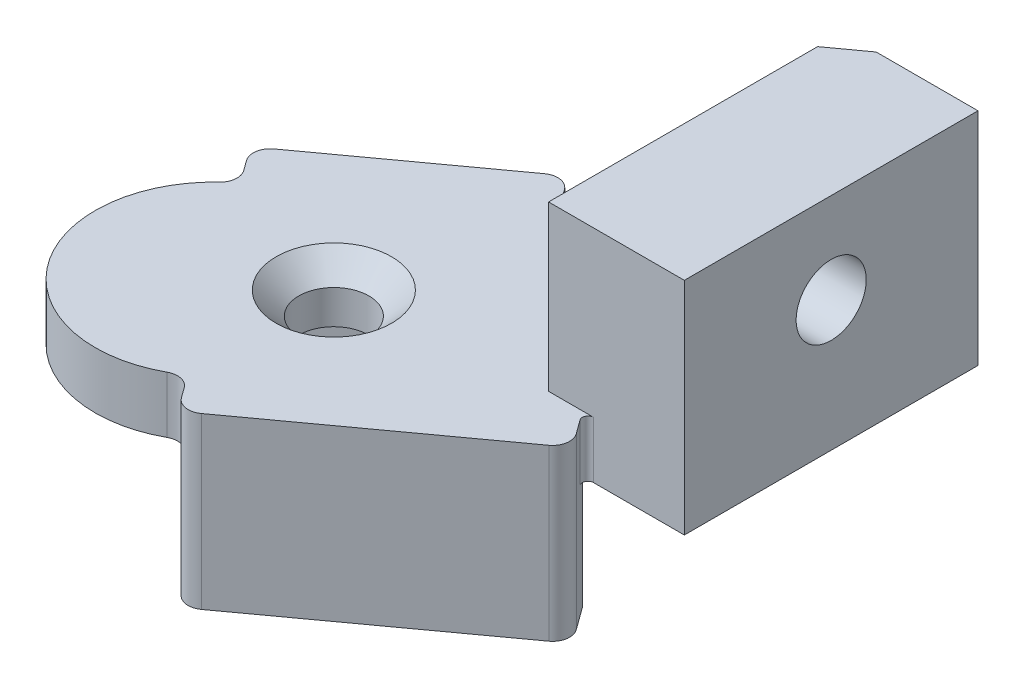
SolidWorks part; units mm, degrees
material "PA 类型 6"
ref_plane "前视基准面" through (0, 0, 0) normal (0, 0, 1) x (1, 0, 0)
ref_plane "上视基准面" through (0, 0, 0) normal (0, 1, 0) x (1, 0, 0)
ref_plane "右视基准面" through (0, 0, 0) normal (1, 0, 0) x (0, 0, -1)
sketch "草图1" plane through (0, 0, 0) normal (0, 1, 0) x (1, 0, 0)
  line L0 (0, 0) -> (0, 12.2017) construction
  line L1 (0, 0) -> (15.21, 0) construction
  line L2 (0, 0) -> (11.3188, 8.2236) construction
  line L3 (10.1244, 13.8452) -> (-6.1542, 2.018)
  line L4 (10.1244, 0.8664) -> (0.0175, -6.4766)
  line L5 (0.0175, -6.4766) -> (-6.1542, 2.018) construction
  line L6 (10.1244, 13.8452) -> (10.1244, 0.8664)
  circle A0 centre (0, 0) radius 1.55
  arc A1 (-6.1542, 2.018) -> (0.0175, -6.4766) centre (-3.0684, -2.2293) ccw
  dimension "D1" = 3.1
  dimension "D2" = 36
  dimension "D3" = 10.5
  dimension "D4" = 10.1244
extrude "基座" add sketch "草图1" along normal blind 2.5
sketch "草图2" plane through (0, 0, 0) normal (0, 1, 0) x (1, 0, 0)
  line L0 (0.0175, -6.4766) -> (1.1931, -8.0947)
  line L1 (1.1931, -8.0947) -> (11.3, -0.7516)
  line L2 (11.3, -0.7516) -> (10.1244, 0.8664)
  line L3 (0.0175, -6.4766) -> (10.1244, 0.8664) construction
  line L4 (10.1244, 0.8664) -> (0.0175, -6.4766)
  line L5 (0, 0) -> (19.4408, 0) construction
  line L6 (0, 0) -> (14.65, 10.6439) construction
  line L7 (10.1244, 13.8452) -> (-6.1542, 2.018) construction
  line L8 (10.1244, 13.8452) -> (-6.1542, 2.018) construction
  line L10 (-7.3298, 3.6361) -> (0.8095, 9.5496)
  line L11 (-6.1542, 2.018) -> (-7.3298, 3.6361)
  line L12 (1.9851, 7.9316) -> (-6.1542, 2.018)
  line L13 (0.8095, 9.5496) -> (1.9851, 7.9316)
  point P20 (1.9851, 7.9316)
  dimension "D1" = 2
extrude "机臂限位" add sketch "草图2" against normal blind 7.5 from surface starting at face at (2.4662, 2.5, -1.7918)
sketch "草图3" plane through (0, 0, 0) normal (0, 1, 0) x (1, 0, 0)
  line L0 (10.1244, 13.8452) -> (14.6244, 13.8452)
  line L1 (14.6244, 13.8452) -> (14.6244, 0.8664)
  line L2 (14.6244, 0.8664) -> (10.1244, 0.8664)
  line L3 (10.1244, 0.8664) -> (10.1244, 13.8452)
  dimension "D1" = 4.5
extrude "限位-1" add sketch "草图3" along normal blind 9.75
sketch "草图4" plane through (0, 0, 0) normal (0, 0, 1) x (1, 0, 0)
  line L0 (14.6244, 9.75) -> (21.1244, 9.75)
  line L1 (21.1244, 9.75) -> (21.1244, -2.25)
  line L2 (21.1244, -2.25) -> (17.6244, -2.25)
  line L3 (17.6244, -2.25) -> (17.6244, 6.5)
  line L4 (17.6244, 6.5) -> (14.6244, 6.5)
  line L5 (14.6244, 9.75) -> (14.6244, 0) construction
  line L6 (14.6244, 6.5) -> (14.6244, 9.75)
  dimension "D1" = 3.25
  dimension "D2" = 3
  dimension "D3" = 8.75
  dimension "D4" = 3.5
chamfer "倒角1" distance 1 angle 45 1 edges at (0, 2.5, 1.55)
sketch "草图5" plane through (10.1244, 0, 0) normal (-1, 0, 0) x (0, 0, 1)
  line L0 (-3.6361, 2.5) -> (-9.5496, 2.5) construction
  line L1 (-4.1515, 5.755) -> (-5.7537, 8.53)
  line L2 (-5.7537, 8.53) -> (-8.9579, 8.53)
  line L3 (-8.9579, 8.53) -> (-10.5601, 5.755)
  line L4 (-10.5601, 5.755) -> (-8.9579, 2.98)
  line L5 (-8.9579, 2.98) -> (-5.7537, 2.98)
  line L6 (-5.7537, 2.98) -> (-4.1515, 5.755)
  line L7 (-7.3558, 10.4317) -> (-7.3558, 1.4425) construction
  line L8 (-13.8452, 9.75) -> (-0.8664, 9.75) construction
  circle A0 centre (-7.3558, 5.755) radius 2.775 construction
  point P14 (-7.3558, 9.75)
  dimension "D1" = 0.48
  dimension "D2" = 5.55
extrude "螺母" cut sketch "草图5" against normal blind 2
sketch "草图6" plane through (10.1244, 0, 0) normal (-1, 0, 0) x (0, 0, 1)
  line L1 (-7.3558, 5.755) -> (-7.3558, 7.9196) construction
  line L2 (-5.7537, 8.53) -> (-8.9579, 8.53) construction
  circle A0 centre (-7.3558, 5.755) radius 1.55
  point P4 (-7.3558, 8.53)
  dimension "D1" = 3.1
extrude "M3螺孔" cut sketch "草图6" against normal up to next
sketch "草图7" plane through (0, 0, 0) normal (0, 1, 0) x (1, 0, 0)
  line L0 (10.1244, 13.8452) -> (8.6244, 12.7553)
  line L1 (10.1244, 13.8452) -> (1.9851, 7.9316) construction
  line L2 (8.6244, 12.7553) -> (8.6244, 0.8664)
  line L3 (8.6244, 0.8664) -> (10.1244, 0.8664)
  line L4 (10.1244, 0.8664) -> (10.1244, 13.8452)
  dimension "D1" = 1.5
extrude "结构补强-1" add sketch "草图7" along normal up to surface (9.75 mm away) from surface up to face at (12.3744, 9.75, -7.3558) starting at face at (0, 2.5, 2.55)
extrude "结构补强螺母位" cut sketch "草图5<2>" along normal through all
sketch "草图5<2>" plane through (10.1244, 0, 0) normal (-1, 0, 0) x (0, 0, 1) same geometry as "草图5"
sketch "草图8" plane through (12.1244, 0, 0) normal (-1, 0, 0) x (0, 0, 1)
  line L0 (-8.9579, 8.53) -> (-5.7537, 8.53) construction
  line L1 (-5.7537, 2.98) -> (-4.1515, 5.755)
  line L2 (-4.1515, 5.755) -> (-5.7537, 8.53)
  line L3 (-5.7537, 8.53) -> (-8.9579, 8.53)
  line L4 (-8.9579, 8.53) -> (-10.5601, 5.755)
  line L5 (-10.5601, 5.755) -> (-8.9579, 2.98)
  line L6 (-8.9579, 2.98) -> (-5.7537, 2.98)
  circle A0 centre (-7.3558, 5.755) radius 2.775 construction
  circle A1 centre (-7.3558, 5.755) radius 1.55
extrude "结构补强螺母位-2" add sketch "草图8" along normal blind 1.5 from surface starting at face at (12.1244, 5.755, -5.8058)
fillet "圆角5" radius 0.75 7 edges at (1.1931, -1.25, 8.0947) (-7.3298, -1.25, -3.6361) (0.0175, 1.25, 6.4766) (-6.1542, 1.25, -2.018) (11.3, -1.25, 0.7516) (1.9851, 1.25, -7.9316) (0.8095, -1.25, -9.5496)
fillet "圆角6" radius 0.25 1 edges at (10.1244, 1.25, -0.8664)
